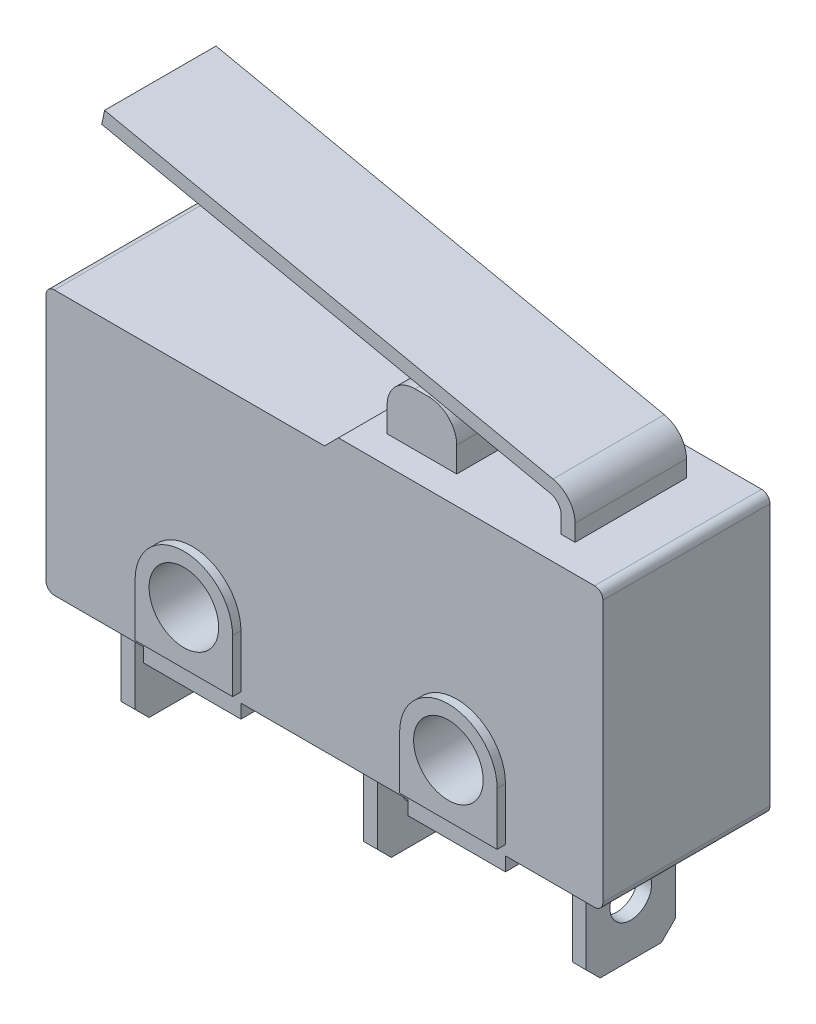
SolidWorks part; units mm, degrees
ref_plane "Спереди" through (0, 0, 0) normal (0, 0, 1) x (1, 0, 0)
ref_plane "Сверху" through (0, 0, 0) normal (0, 1, 0) x (1, 0, 0)
ref_plane "Справа" through (0, 0, 0) normal (1, 0, 0) x (0, 0, -1)
sketch "Sketch1" plane through (0, 0, 0) normal (0, 0, 1) x (1, 0, 0)
  line L1 (10, 5.25) -> (-10, 5.25)
  line L2 (10, 5.25) -> (10, -5.25)
  line L3 (10, -5.25) -> (-10, -5.25)
  line L4 (-10, 5.25) -> (-10, -5.25)
  line L5 (10, 5.25) -> (-10, -5.25) construction
  line L6 (10, -5.25) -> (-10, 5.25) construction
  point P0 (0, 0)
  dimension "D1" = 20
  dimension "D2" = 10.5
extrude "Boss-Extrude1" add sketch "Sketch1" along normal mid plane 6
sketch "Sketch2" plane through (0, 0, 0) normal (0, 0, 1) x (1, 0, 0)
  line L0 (0, 5.25) -> (0, 4.75)
  line L1 (10, 5.25) -> (-10, 5.25) construction
  line L2 (0, 4.75) -> (-10, 4.75)
  line L3 (-10, 5.25) -> (-10, -5.25) construction
  line L4 (10, -5.25) -> (10, 5.25) construction
  line L5 (0, 5.25) -> (0, -5.3036) construction
  line L8 (-10, -5.25) -> (10, -5.25) construction
  line L9 (-3, -5.25) -> (3, -5.25)
  line L10 (-3, -5.25) -> (-3, -4.75)
  line L11 (-3, -4.75) -> (3, -4.75)
  line L12 (3, -5.25) -> (3, -4.75)
  line L13 (10, -5.25) -> (10, -4.75)
  line L14 (-10, -5.25) -> (-6.5, -5.25)
  line L15 (-10, -5.25) -> (-10, -4.75)
  line L16 (-10, -4.75) -> (-6.5, -4.75)
  line L17 (-6.5, -5.25) -> (-6.5, -4.75)
  line L18 (10, -5.25) -> (6.5, -5.25)
  line L19 (6.5, -5.25) -> (6.5, -4.75)
  line L20 (10, -4.75) -> (6.5, -4.75)
  line L21 (0, 5.25) -> (-10, 5.25)
  line L22 (-10, 5.25) -> (-10, 4.75)
  point P16 (0, -4.75)
  point P22 (-6.5, -5)
  dimension "D1" = 0.5
  dimension "D2" = 10
  dimension "D3" = 6
  dimension "D4" = 0.5
  dimension "D5" = 3.5
extrude "Cut-Extrude1" cut sketch "Sketch2" against normal through all both and the other way through all
sketch "Sketch3" plane through (0, 0, 0) normal (0, 0, 1) x (1, 0, 0)
  line L1 (-10, -5.25) -> (10, -5.25) construction
  line L2 (-4.75, -5.25) -> (-4.75, 4.75) construction
  line L3 (-6.5, -5.25) -> (-3, -5.25) construction
  line L4 (-10, 4.75) -> (0, 4.75) construction
  line L5 (4.75, -5.25) -> (4.75, 5.25) construction
  line L6 (3, -5.25) -> (6.5, -5.25) construction
  line L7 (10, 5.25) -> (0, 5.25) construction
  circle A0 centre (-4.75, -2.5) radius 1.25
  circle A1 centre (4.75, -2.5) radius 1.25
  point P4 (0, 0)
  dimension "D1" = 12
  dimension "D2" = 4
extrude "Cut-Extrude2" cut sketch "Sketch3" against normal through all both and the other way through all
sketch "Sketch4" plane through (0, -4.75, 0) normal (0, -1, 0) x (1, 0, 0)
  line L0 (-10, 0) -> (10, 0) construction
  line L1 (-10, -3) -> (-10, 3) construction
  line L2 (10, -3) -> (10, 3) construction
  line L3 (-8.2, 1.6) -> (-8.2, -1.6)
  line L4 (0.5, 1.6) -> (0.5, -1.6)
  line L5 (8, 1.6) -> (8, -1.6)
  point P9 (-8.2, 0)
  point P12 (0.5, 0)
  point P15 (8, 0)
  dimension "D1" = 3.2
  dimension "D2" = 10.5
  dimension "D3" = 2
  dimension "D4" = 1.8
extrude "Extrude-Thin1" add sketch "Sketch4" along normal blind 4 thin thin type one direction wall 0.5
chamfer "Chamfer1" distance 0.5 angle 45 6 edges at (-8.45, -8.75, 1.6) (-8.45, -8.75, -1.6) (7.75, -8.75, -1.6) (7.75, -8.75, 1.6) (0.25, -8.75, 1.6) (0.25, -8.75, -1.6)
sketch "Sketch5" plane through (0, 0, 0) normal (1, 0, 0) x (0, 0, -1)
  line L0 (0, -4.75) -> (0, -8.75) construction
  line L1 (3, -4.75) -> (-3, -4.75) construction
  line L2 (-1.1, -8.75) -> (1.1, -8.75) construction
  line L3 (-1.6, -4.75) -> (1.6, -4.75) construction
  circle A0 centre (0, -6.75) radius 0.75
  point P8 (0, -4.75)
  point P11 (0, 0)
  point P12 (0, -6.75)
  dimension "D1" = 1.5
extrude "Cut-Extrude3" cut sketch "Sketch5" along normal through all both and the other way through all
chamfer "Chamfer2" distance 0.5 angle 45 1 edges at (0, 5.25, 0)
fillet "Fillet1" radius 0.3 4 edges at (-10, -4.75, 0) (10, -4.75, 0) (10, 5.25, 0) (-10, 4.75, 0)
sketch "Sketch6" plane through (0, 0, 3) normal (0, 0, 1) x (1, 0, 0)
  line L0 (-6.5, -2.5) -> (-6.5, -4.4)
  line L1 (-6.5, -4.4) -> (-3, -4.4)
  line L2 (-3, -4.4) -> (-3, -2.5)
  line L3 (0, 0) -> (0, -4.6325) construction
  line L4 (3, -4.4) -> (3, -2.5)
  line L5 (6.5, -4.4) -> (3, -4.4)
  line L6 (6.5, -2.5) -> (6.5, -4.4)
  arc A0 (-3, -2.5) -> (-6.5, -2.5) centre (-4.75, -2.5) ccw
  circle A2 centre (-4.75, -2.5) radius 1.25 construction
  circle A3 centre (-4.75, -2.5) radius 1.25
  arc A4 (3, -2.5) -> (6.5, -2.5) centre (4.75, -2.5) cw
  circle A5 centre (4.75, -2.5) radius 1.25
  dimension "D1" = 0.5
  dimension "D2" = 1.9
extrude "Boss-Extrude2" add sketch "Sketch6" along normal blind 0.3
mirror "Mirror1" about plane through (0, 0, 0) normal (0, 0, 1) of "Boss-Extrude2"
sketch "Sketch7" plane through (0, 0, 0) normal (0, 0, 1) x (1, 0, 0)
  line L0 (7.5, 5.25) -> (7.5, 5.8449)
  line L1 (9.7, 5.25) -> (0.5, 5.25) construction
  line L2 (7.1038, 6.3341) -> (-9, 9.75)
  line L3 (-9.7, 4.75) -> (0, 4.75) construction
  line L4 (10, -4.45) -> (10, 4.95) construction
  line L5 (-10, 4.45) -> (-10, -4.45) construction
  arc A0 (7.5, 5.8449) -> (7.1038, 6.3341) centre (7, 5.8449) ccw
  point P9 (7.5, 6.2841)
  point P14 (7.5, 6.25)
  dimension "D5" = 0.5
  dimension "D1" = 5
  dimension "D2" = 2.5
  dimension "D3" = 1
  dimension "D4" = 1
extrude "Extrude-Thin2" add sketch "Sketch7" along normal mid plane 4 thin thin type one direction wall 0.5
sketch "Sketch8" plane through (0, 5.25, 0) normal (0, 1, 0) x (1, 0, 0)
  line L0 (0.5, 3) -> (0.5, -3) construction
  line L1 (1.25, 2) -> (3.75, 2)
  line L2 (1.25, 2) -> (1.25, -2)
  line L3 (1.25, -2) -> (3.75, -2)
  line L4 (3.75, 2) -> (3.75, -2)
  line L5 (1.25, 2) -> (3.75, -2) construction
  line L6 (1.25, -2) -> (3.75, 2) construction
  point P0 (2.5, 0)
  point P5 (0, 0)
  point P9 (0, 0)
  dimension "D1" = 4
  dimension "D2" = 2.5
  dimension "D3" = 2
extrude "Boss-Extrude3" add sketch "Sketch8" along normal blind 1.9 separate body
fillet "Fillet2" radius 1 2 edges at (3.75, 7.15, 0) (1.25, 7.15, 0)
